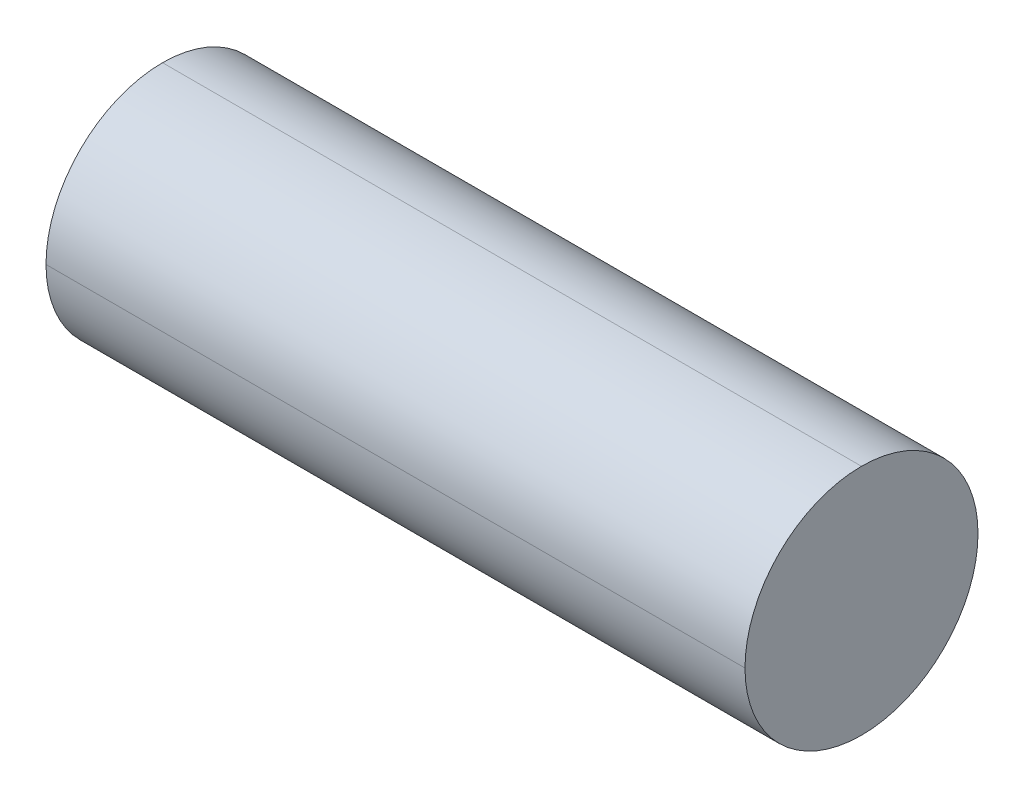
SolidWorks part; units mm, degrees
ref_plane "Front Plane" through (0, 0, 0) normal (0, 0, 1) x (1, 0, 0)
ref_plane "Top Plane" through (0, 0, 0) normal (0, 1, 0) x (1, 0, 0)
ref_plane "Right Plane" through (0, 0, 0) normal (1, 0, 0) x (0, 0, -1)
sketch "Sketch1" plane through (0, 0, 0) normal (0, 0, 1) x (1, 0, 0)
  line L1 (0, 0) -> (60, 0)
  line L2 (0, 0) -> (0, 20)
  line L3 (0, 20) -> (60, 20)
  line L4 (60, 0) -> (60, 20)
  dimension "D1" = 60
  dimension "D2" = 20
extrude "Boss-Extrude1" add sketch "Sketch1" along normal blind 20
fillet "Fillet1" radius 10 4 edges at (30, 0, 0) (30, 0, 20) (30, 20, 20) (30, 20, 0)
